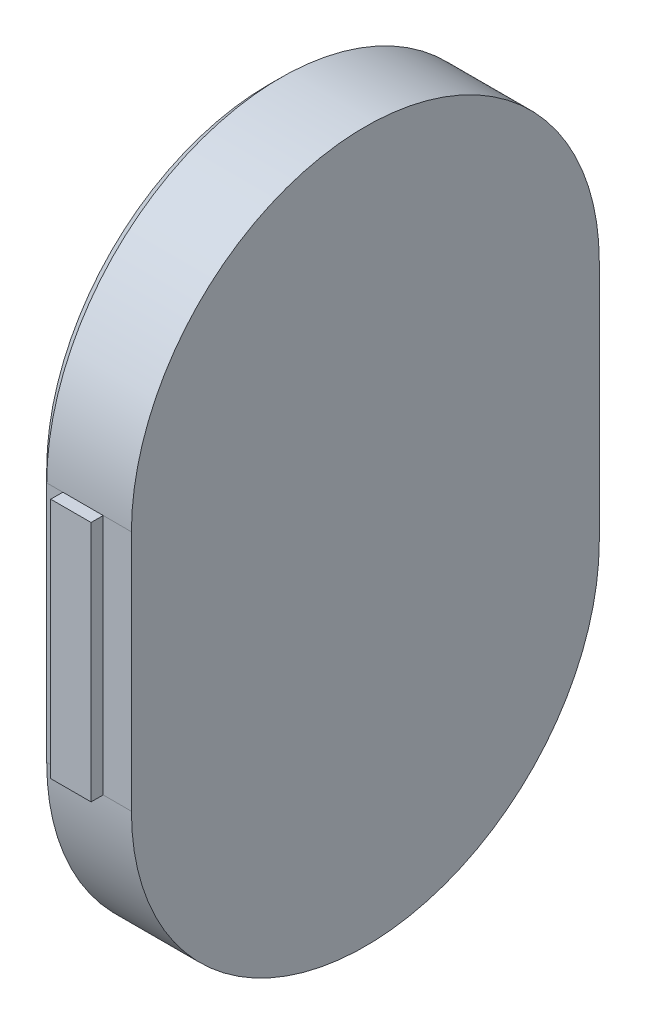
SolidWorks part; units mm, degrees
ref_plane "Front Plane" through (0, 0, 0) normal (0, 0, 1) x (1, 0, 0)
ref_plane "Top Plane" through (0, 0, 0) normal (0, 1, 0) x (1, 0, 0)
ref_plane "Right Plane" through (0, 0, 0) normal (1, 0, 0) x (0, 0, -1)
sketch "Sketch1" plane through (0, 0, 0) normal (1, 0, 0) x (0, 0, -1)
  line L0 (-94.1, 53) -> (-94.1, 59)
  line L1 (-82.5, 59) -> (-82.5, 53)
  arc A0 (-82.5, 53) -> (-88.3, 47.2) centre (-88.3, 53) cw
  arc A1 (-88.3, 47.2) -> (-94.1, 53) centre (-88.3, 53) cw
  arc A2 (-94.1, 59) -> (-88.3, 64.8) centre (-88.3, 59) cw
  arc A3 (-88.3, 64.8) -> (-82.5, 59) centre (-88.3, 59) cw
extrude "Boss-Extrude1" add sketch "Sketch1" along normal blind 2.4 from offset 38 offset against normal yes
chamfer "Chamfer1" distance 0.3 angle 45 4 edges at (-38, 47.2, 88.3) (-38, 56, 82.5) (-38, 56, 94.1) (-38, 64.8, 88.3)
sketch "Sketch2" plane through (0, 0, 0) normal (0, 0, 1) x (1, 0, 0)
  line L1 (-37.3, 53) -> (-36.3, 53)
  line L2 (-37.3, 53) -> (-37.3, 59)
  line L3 (-37.3, 59) -> (-36.3, 59)
  line L4 (-36.3, 53) -> (-36.3, 59)
extrude "Boss-Extrude2" add sketch "Sketch2" along normal blind 0.31 from offset 82.2
sketch "Sketch3" plane through (0, 0, 0) normal (0, 0, 1) x (1, 0, 0)
  line L1 (-37.3, 53) -> (-36.3, 53)
  line L2 (-37.3, 53) -> (-37.3, 59)
  line L3 (-37.3, 59) -> (-36.3, 59)
  line L4 (-36.3, 53) -> (-36.3, 59)
extrude "Boss-Extrude3" add sketch "Sketch3" along normal blind 0.31 from offset 94.09
sketch "Sketch4" plane through (0, 0, 0) normal (0, 0, 1) x (1, 0, 0)
  line L1 (-38.1, 47.1) -> (-37.4, 47.1)
  line L2 (-38.1, 47.1) -> (-38.1, 48.4)
  line L3 (-38.1, 48.4) -> (-37.4, 48.4)
  line L4 (-37.4, 47.1) -> (-37.4, 48.4)
extrude "Boss-Extrude4" add sketch "Sketch4" along normal blind 3 from offset 86.8 separate body
combine bodies "Combine1" operation type subtract main body 103 bodies to subtract 104
